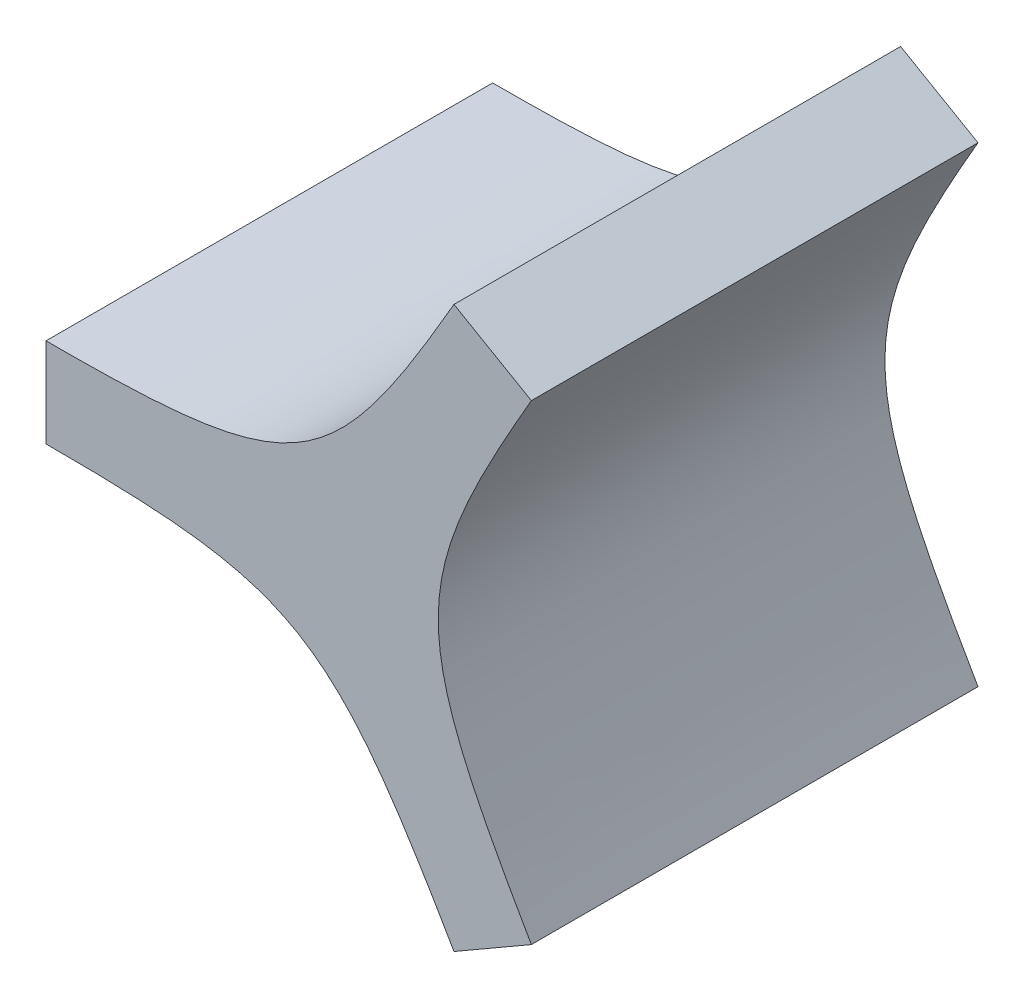
SolidWorks part; units mm, degrees
ref_plane "Front Plane" through (0, 0, 0) normal (0, 0, 1) x (1, 0, 0)
ref_plane "Top Plane" through (0, 0, 0) normal (0, 1, 0) x (1, 0, 0)
ref_plane "Right Plane" through (0, 0, 0) normal (1, 0, 0) x (0, 0, -1)
sketch "Sketch1" plane through (0, 0, 0) normal (0, 0, 1) x (1, 0, 0)
  line L0 (6.299, 7.9103) -> (3.701, 9.4103)
  line L1 (-10, 1.5) -> (0, 1.5) construction
  line L2 (-10, 1.5) -> (-10, -1.5)
  line L3 (-10, -1.5) -> (0, -1.5) construction
  line L4 (0, 1.5) -> (0, -1.5) construction
  line L5 (6.299, 7.9103) -> (1.299, -0.75) construction
  line L6 (3.701, 9.4103) -> (-1.299, 0.75) construction
  line L7 (1.299, -0.75) -> (-1.299, 0.75) construction
  line L8 (3.701, -9.4103) -> (6.299, -7.9103)
  line L9 (3.701, -9.4103) -> (-1.299, -0.75) construction
  line L10 (6.299, -7.9103) -> (1.299, 0.75) construction
  line L11 (-1.299, -0.75) -> (1.299, 0.75) construction
  spline S0 degree 3 poles (-10, 1.5) (-1.6667, 1.5) (-0.4657, 2.1934) (3.701, 9.4103) knots 0 0 0 0 1 1 1 1
  spline S1 degree 3 poles (6.299, 7.9103) (2.1324, 0.6934) (2.1324, -0.6934) (6.299, -7.9103) knots 0 0 0 0 1 1 1 1
  spline S2 degree 3 poles (3.701, -9.4103) (-0.4657, -2.1934) (-1.6667, -1.5) (-10, -1.5) knots 0 0 0 0 1 1 1 1
  point P4 (0, 0)
  point P16 (0, 0)
  point P21 (0, 0)
  dimension "D4" = 25
  dimension "D5" = 25
  dimension "D1" = 3
  dimension "D2" = 10
  dimension "D3" = 3
extrude "Boss-Extrude1" add sketch "Sketch1" along normal mid plane 15 from offset 75
